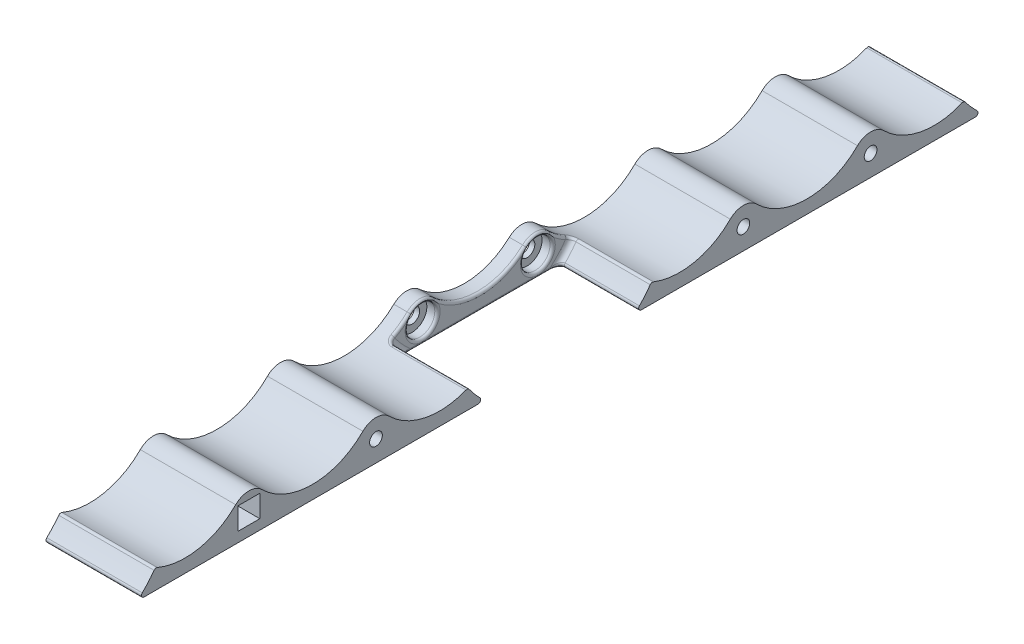
SolidWorks part; units mm, degrees
ref_plane "Front Plane" through (0, 0, 0) normal (0, 0, 1) x (1, 0, 0)
ref_plane "Top Plane" through (0, 0, 0) normal (0, 1, 0) x (1, 0, 0)
ref_plane "Right Plane" through (0, 0, 0) normal (1, 0, 0) x (0, 0, -1)
sketch "Sketch1" plane through (0, 0, 0) normal (1, 0, 0) x (0, 0, -1)
  line L0 (-126.5656, -24.6062) -> (126.5656, -24.6062)
  arc A0 (126.5656, -24.6062) -> (121.1052, -18.6881) centre (148.1579, 0.7938) cw
  arc A1 (-126.5656, -24.6062) -> (-121.1052, -18.6881) centre (-148.1579, 0.7937) ccw
  circle A2 centre (-93.1246, -18.3223) radius 5.5562 construction
  arc A3 (-93.1246, -9.0244) -> (-55.0246, -9.0244) centre (-74.0746, 0.7938) ccw construction
  circle A4 centre (-55.0246, -18.3223) radius 5.5562 construction
  arc A5 (-55.0246, -9.0244) -> (-17.2998, -9.7206) centre (-35.9746, 0.7938) ccw construction
  circle A6 centre (-17.2515, -18.6426) radius 5.5562 construction
  arc A7 (-17.2998, -9.7206) -> (17.2998, -9.7206) centre (0, 0) ccw construction
  circle A8 centre (17.2515, -18.6426) radius 5.5562 construction
  arc A9 (17.2998, -9.7206) -> (55.0246, -9.0244) centre (35.9746, 0.7937) ccw construction
  circle A10 centre (55.0246, -18.3223) radius 5.5562 construction
  circle A11 centre (93.1246, -18.3223) radius 5.5562 construction
  arc A12 (93.1246, -9.0244) -> (131.0767, -9.3061) centre (112.1746, 0.7937) ccw construction
  arc A13 (55.0246, -9.0244) -> (93.1246, -9.0244) centre (74.0746, 0.7937) ccw construction
  arc A14 (-89.2025, -14.3866) -> (-97.0466, -14.3866) centre (-93.1246, -18.3223) ccw
  arc A15 (-89.2025, -14.3866) -> (-58.9466, -14.3866) centre (-74.0746, 0.7938) ccw
  arc A16 (-51.1025, -14.3866) -> (-58.9466, -14.3866) centre (-55.0246, -18.3223) ccw
  arc A17 (-51.1025, -14.3866) -> (-21.1062, -14.641) centre (-35.9746, 0.7938) ccw
  arc A18 (-13.4777, -14.5645) -> (-21.1062, -14.641) centre (-17.2515, -18.6426) ccw
  arc A19 (-13.4777, -14.5645) -> (13.4777, -14.5645) centre (0, 0) ccw
  arc A20 (21.1062, -14.641) -> (13.4777, -14.5645) centre (17.2515, -18.6426) ccw
  arc A21 (21.1062, -14.641) -> (51.1025, -14.3866) centre (35.9746, 0.7937) ccw
  arc A22 (58.9466, -14.3866) -> (51.1025, -14.3866) centre (55.0246, -18.3223) ccw
  arc A23 (97.0466, -14.3866) -> (89.2025, -14.3866) centre (93.1246, -18.3223) ccw
  arc A24 (97.0466, -14.3866) -> (121.1052, -18.6881) centre (112.1746, 0.7937) ccw
  arc A25 (58.9466, -14.3866) -> (89.2025, -14.3866) centre (74.0746, 0.7937) ccw
  arc A26 (-131.0767, -9.3061) -> (-93.1246, -9.0244) centre (-112.1746, 0.7937) ccw construction
  arc A27 (-121.1052, -18.6881) -> (-97.0466, -14.3866) centre (-112.1746, 0.7937) ccw
  arc A28 (-138.4024, 32.6719) -> (-143.3009, 33.7755) centre (-148.1579, 0.7937) ccw construction
  circle A29 centre (148.1579, 0.7938) radius 2.032 construction
  point P3 (0, -24.6062)
  point P8 (150.1899, -0.8345)
  point P9 (0, 0)
  dimension "D1" = 24.6062
extrude "Boss-Extrude1" add sketch "Sketch1" along normal up to surface (28.575 mm away)
sketch "Sketch2" plane through (28.575, 0, 0) normal (1, 0, 0) x (0, 0, -1)
  circle A0 centre (0, 0) radius 33.3375
  dimension "D1" = 66.675
extrude "Cut-Extrude1" cut sketch "Sketch2" against normal blind 23.8125
sketch "Sketch3" plane through (28.575, 0, 0) normal (1, 0, 0) x (0, 0, -1)
  line L9 (-89.8226, -15.0203) -> (-96.4266, -15.0203)
  line L10 (-89.8226, -21.6243) -> (-89.8226, -15.0203)
  line L11 (-96.4266, -21.6243) -> (-89.8226, -21.6243)
  line L12 (-96.4266, -15.0203) -> (-96.4266, -21.6243)
  line L13 (-89.8226, -15.0203) -> (-96.4266, -15.0203)
  line L14 (-89.8226, -21.6243) -> (-89.8226, -15.0203)
  line L15 (-96.4266, -21.6243) -> (-89.8226, -21.6243)
  line L16 (-96.4266, -15.0203) -> (-96.4266, -21.6243)
  dimension "D1" = 0.127
extrude "Cut-Extrude2" cut sketch "Sketch3" against normal through all
sketch "Sketch4" plane through (28.575, 0, 0) normal (1, 0, 0) x (0, 0, -1)
  circle A0 centre (93.1246, -18.3223) radius 2.032 construction
  point P0 (-55.0246, -18.3223)
  point P3 (55.0246, -18.3223)
  point P6 (93.1246, -18.3223)
hole_wizard "#8 Clearance Hole1" positions "Sketch4" profile "Sketch5" hole size "#8" standard "ANSI Inch" end condition up to next
sketch "Sketch5" plane through (28.575, -18.3223, 55.0246) normal (0, 1, 0) x (0, 0, -1)
  line L0 (0, 0) -> (0, 28.575)
  line L1 (0, 28.575) -> (1.905, 28.575)
  line L2 (1.905, 28.575) -> (1.905, 0)
  line L5 (1.905, 0) -> (0, 0)
  line L11 (0, -6.35) -> (0, 107.95) construction
  dimension "Thru Hole Dia." = 3.81
  dimension "Thru Hole Depth" = 28.575
sketch "Sketch6" plane through (4.7625, 0, 0) normal (1, 0, 0) x (0, 0, -1)
  circle A0 centre (-17.2515, -18.6426) radius 4.445
  circle A1 centre (17.2515, -18.6426) radius 4.445
  dimension "D1" = 8.89
extrude "Cut-Extrude3" cut sketch "Sketch6" against normal blind 3.175
sketch "Sketch7" plane through (1.5875, 0, 0) normal (1, 0, 0) x (0, 0, -1)
  point P0 (-17.2515, -18.6426)
  point P3 (17.2515, -18.6426)
hole_wizard "#8 Clearance Hole2" positions "Sketch7" profile "Sketch8" hole size "#8" standard "ANSI Inch" end condition up to next
sketch "Sketch8" plane through (1.5875, -18.6426, 17.2515) normal (0, 1, 0) x (0, 0, -1)
  line L0 (0, 0) -> (0, 1.5875)
  line L1 (0, 1.5875) -> (2.286, 1.5875)
  line L2 (2.286, 1.5875) -> (2.286, 0)
  line L5 (2.286, 0) -> (0, 0)
  line L11 (0, -6.35) -> (0, 107.95) construction
  dimension "Thru Hole Dia." = 4.572
  dimension "Thru Hole Depth" = 1.5875
fillet "Fillet1" radius 1.5875 2 edges at (4.7625, -21.8856, -25.1478) (4.7625, -21.8856, 25.1478)
fillet "Fillet2" radius 0.7937 20 edges at (17.4625, -18.8803, -27.4758) (5.116, -18.6353, -26.9296) (4.7625, -16.5891, -23.4393) (4.7625, -13.0866, -17.3072) (17.4625, -18.8803, 27.4758) (5.3711, -18.7415, 27.1614) (4.7625, -16.5891, 23.4393) (4.7625, -13.0866, 17.3072) (17.4625, -24.6062, 22.4927) (5.2999, -24.6062, 21.9001) (17.4625, -24.6062, -22.4927) (5.5963, -24.6062, -22.2096) (4.7625, -18.6426, -21.6965) (4.7625, -18.6426, 12.8065) (4.7625, -19.8437, 0) (4.7625, -24.6062, 0) (14.2875, -24.6062, -126.5656) (14.2875, -18.6881, -121.1052) (14.2875, -24.6062, 126.5656) (14.2875, -18.6881, 121.1052)
